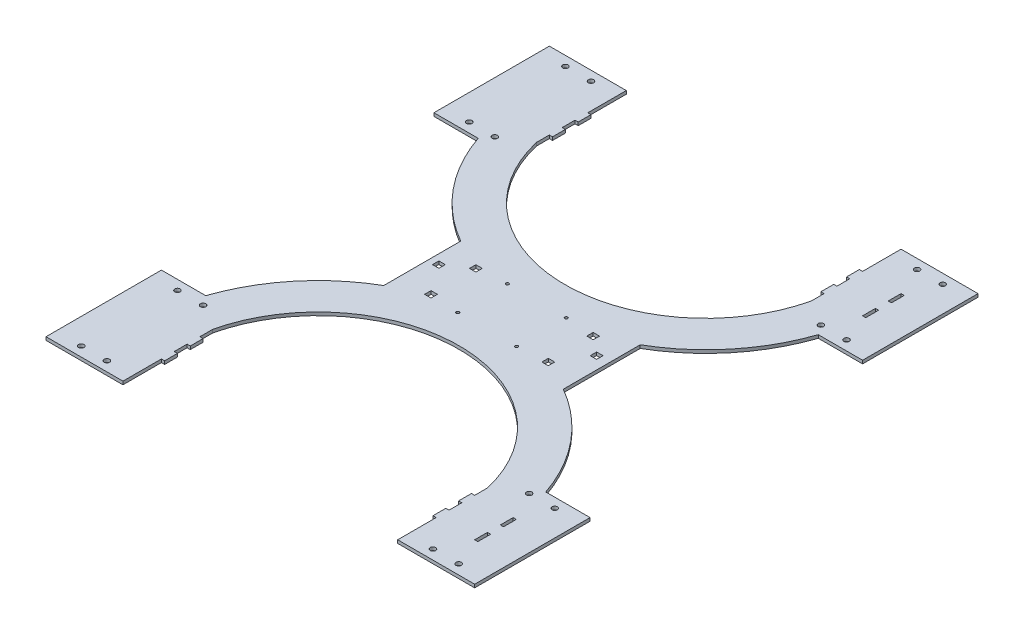
SolidWorks part; units mm, degrees
ref_plane "Front Plane" through (0, 0, 0) normal (0, 0, 1) x (1, 0, 0)
ref_plane "Top Plane" through (0, 0, 0) normal (0, 1, 0) x (1, 0, 0)
ref_plane "Right Plane" through (0, 0, 0) normal (1, 0, 0) x (0, 0, -1)
sketch "Sketch1" plane through (0, 0, 0) normal (0, 1, 0) x (1, 0, 0)
  line L47 (-136.0442, 57.15) -> (-212.2442, 57.15)
  line L49 (-212.2442, -57.15) -> (-168.3648, -57.15)
  line L51 (-88.9, -153.9793) -> (-88.9, -230.1793)
  line L60 (136.0442, 57.15) -> (212.2442, 57.15)
  line L62 (212.2442, -57.15) -> (168.3648, -57.15)
  line L64 (88.9, -153.9793) -> (88.9, -230.1793)
  line L65 (-136.0442, -31.75) -> (-136.0442, -19.05)
  line L66 (0, 0) -> (136.0442, 0) construction
  line L67 (0, -167.5048) -> (0, 0) construction
  line L68 (-88.9, -192.0793) -> (88.9, -192.0793) construction
  line L72 (136.0442, -365.1086) -> (136.0442, -352.4086)
  line L98 (212.2442, 57.15) -> (212.2442, -57.15)
  line L103 (-212.2442, 57.15) -> (-212.2442, -57.15)
  line L133 (136.0442, 19.05) -> (136.0442, 57.15)
  line L142 (-136.0442, -352.4086) -> (-136.0442, -365.1086)
  line L151 (136.0442, -403.2086) -> (136.0442, -441.3086)
  line L152 (-212.2442, -441.3086) -> (-212.2442, -327.0086)
  line L153 (212.2442, -441.3086) -> (212.2442, -327.0086)
  line L154 (212.2442, -327.0086) -> (168.3648, -327.0086)
  line L155 (136.0442, -441.3086) -> (212.2442, -441.3086)
  line L159 (-212.2442, -327.0086) -> (-168.3648, -327.0086)
  line L160 (-136.0442, -441.3086) -> (-212.2442, -441.3086)
  line L166 (-161.4442, 47.625) -> (-186.8442, 47.625) construction
  line L167 (161.4442, 47.625) -> (186.8442, 47.625) construction
  line L168 (186.8442, 47.625) -> (186.8442, -47.625) construction
  line L169 (186.8442, -47.625) -> (161.4442, -47.625) construction
  line L170 (-186.8442, 47.625) -> (-186.8442, -47.625) construction
  line L171 (-186.8442, -47.625) -> (-161.4442, -47.625) construction
  line L172 (-29.1465, -167.5048) -> (29.1465, -167.5048) construction
  line L173 (29.1465, -167.5048) -> (29.1465, -216.6538) construction
  line L174 (29.1465, -216.6538) -> (-29.1465, -216.6538) construction
  line L175 (174.1442, -6.35) -> (174.1442, 6.35) construction
  line L176 (-136.0442, -19.05) -> (-132.8692, -19.05)
  line L177 (-132.8692, -19.05) -> (-132.8692, -6.35)
  line L178 (-132.8692, -6.35) -> (-136.0442, -6.35)
  line L179 (-136.0442, -6.35) -> (-136.0442, 6.35)
  line L180 (-136.0442, 6.35) -> (-132.8692, 6.35)
  line L181 (-132.8692, 6.35) -> (-132.8692, 19.05)
  line L182 (-132.8692, 19.05) -> (-136.0442, 19.05)
  line L183 (-136.0442, 19.05) -> (-136.0442, 57.15)
  line L184 (-136.0442, 0) -> (0, 0) construction
  line L185 (-136.0442, -365.1086) -> (-132.8692, -365.1086)
  line L186 (-132.8692, -365.1086) -> (-132.8692, -377.8086)
  line L187 (-132.8692, -377.8086) -> (-136.0442, -377.8086)
  line L188 (-136.0442, -377.8086) -> (-136.0442, -390.5086)
  line L189 (-136.0442, -390.5086) -> (-132.8692, -390.5086)
  line L190 (-132.8692, -390.5086) -> (-132.8692, -403.2086)
  line L191 (-132.8692, -403.2086) -> (-136.0442, -403.2086)
  line L192 (-136.0442, -403.2086) -> (-136.0442, -441.3086)
  line L193 (136.0442, 19.05) -> (132.8692, 19.05)
  line L194 (132.8692, 19.05) -> (132.8692, 6.35)
  line L195 (132.8692, 6.35) -> (136.0442, 6.35)
  line L196 (136.0442, 6.35) -> (136.0442, -6.35)
  line L197 (136.0442, -6.35) -> (132.8692, -6.35)
  line L198 (132.8692, -6.35) -> (132.8692, -19.05)
  line L199 (132.8692, -19.05) -> (136.0442, -19.05)
  line L200 (136.0442, -19.05) -> (136.0442, -31.75)
  line L201 (132.8692, -365.1086) -> (136.0442, -365.1086)
  line L202 (132.8692, -377.8086) -> (132.8692, -365.1086)
  line L203 (136.0442, -377.8086) -> (132.8692, -377.8086)
  line L204 (136.0442, -390.5086) -> (136.0442, -377.8086)
  line L205 (132.8692, -390.5086) -> (136.0442, -390.5086)
  line L206 (132.8692, -403.2086) -> (132.8692, -390.5086)
  line L207 (136.0442, -403.2086) -> (132.8692, -403.2086)
  line L208 (174.1442, 19.05) -> (177.3192, 19.05)
  line L209 (174.1442, 19.05) -> (174.1442, 6.35)
  line L210 (174.1442, 6.35) -> (177.3192, 6.35)
  line L211 (177.3192, 19.05) -> (177.3192, 6.35)
  line L212 (174.1442, -6.35) -> (177.3192, -6.35)
  line L213 (174.1442, -6.35) -> (174.1442, -19.05)
  line L214 (174.1442, -19.05) -> (177.3192, -19.05)
  line L215 (177.3192, -6.35) -> (177.3192, -19.05)
  line L216 (136.0442, 0) -> (174.1442, 0) construction
  line L217 (174.1442, -377.8086) -> (174.1442, -365.1086)
  line L218 (174.1442, -365.1086) -> (177.3192, -365.1086)
  line L219 (177.3192, -377.8086) -> (177.3192, -365.1086)
  line L220 (174.1442, -377.8086) -> (177.3192, -377.8086)
  line L221 (174.1442, -390.5086) -> (177.3192, -390.5086)
  line L222 (174.1442, -403.2086) -> (174.1442, -390.5086)
  line L223 (177.3192, -403.2086) -> (177.3192, -390.5086)
  line L224 (174.1442, -403.2086) -> (177.3192, -403.2086)
  line L225 (-54.7929, -173.0293) -> (-54.7929, -192.0793) construction
  line L226 (-61.1429, -166.6793) -> (-54.7929, -166.6793)
  line L227 (-61.1429, -166.6793) -> (-61.1429, -173.0293)
  line L228 (-61.1429, -173.0293) -> (-54.7929, -173.0293)
  line L229 (-54.7929, -166.6793) -> (-54.7929, -173.0293)
  line L230 (54.9714, -166.6793) -> (61.3214, -166.6793)
  line L231 (54.9714, -166.6793) -> (54.9714, -173.0293)
  line L232 (54.9714, -173.0293) -> (61.3214, -173.0293)
  line L233 (61.3214, -166.6793) -> (61.3214, -173.0293)
  line L234 (54.9714, -211.1293) -> (61.3214, -211.1293)
  line L235 (54.9714, -211.1293) -> (54.9714, -217.4793)
  line L236 (54.9714, -217.4793) -> (61.3214, -217.4793)
  line L237 (61.3214, -211.1293) -> (61.3214, -217.4793)
  line L238 (-61.1429, -211.1293) -> (-54.7929, -211.1293)
  line L239 (-61.1429, -211.1293) -> (-61.1429, -217.4793)
  line L240 (-61.1429, -217.4793) -> (-54.7929, -217.4793)
  line L241 (-54.7929, -211.1293) -> (-54.7929, -217.4793)
  line L242 (73.4754, -181.7472) -> (79.8254, -181.7472)
  line L243 (73.4754, -181.7472) -> (73.4754, -188.0972)
  line L244 (73.4754, -188.0972) -> (79.8254, -188.0972)
  line L245 (79.8254, -181.7472) -> (79.8254, -188.0972)
  line L246 (-82.7346, -181.7472) -> (-76.3846, -181.7472)
  line L247 (-82.7346, -181.7472) -> (-82.7346, -188.0972)
  line L248 (-82.7346, -188.0972) -> (-76.3846, -188.0972)
  line L249 (-76.3846, -181.7472) -> (-76.3846, -188.0972)
  arc A14 (88.9, -153.9793) -> (168.3648, -57.15) centre (0, 0) ccw
  arc A15 (-88.9, -153.9793) -> (-168.3648, -57.15) centre (0, 0) cw
  arc A23 (88.9, -230.1793) -> (168.3648, -327.0086) centre (0, -384.1586) cw
  arc A26 (-88.9, -230.1793) -> (-168.3648, -327.0086) centre (0, -384.1586) ccw
  circle A27 centre (186.8442, 47.625) radius 2.667
  circle A28 centre (161.4442, 47.625) radius 2.667
  circle A29 centre (186.8442, -47.625) radius 2.667
  circle A30 centre (161.4442, -47.625) radius 2.667
  circle A31 centre (161.4442, -336.5336) radius 2.667
  circle A32 centre (186.8442, -336.5336) radius 2.667
  circle A33 centre (186.8442, -431.7836) radius 2.667
  circle A34 centre (161.4442, -431.7836) radius 2.667
  circle A35 centre (-186.8442, 47.625) radius 2.667
  circle A36 centre (-161.4442, 47.625) radius 2.667
  circle A37 centre (-186.8442, -47.625) radius 2.667
  circle A38 centre (-161.4442, -47.625) radius 2.667
  circle A39 centre (-186.8442, -336.5336) radius 2.667
  circle A40 centre (-161.4442, -336.5336) radius 2.667
  circle A41 centre (-161.4442, -431.7836) radius 2.667
  circle A42 centre (-186.8442, -431.7836) radius 2.667
  circle A43 centre (-29.1465, -167.5048) radius 1.4605
  circle A44 centre (29.1465, -167.5048) radius 1.4605
  circle A45 centre (29.1465, -216.6538) radius 1.4605
  circle A46 centre (-29.1465, -216.6538) radius 1.4605
  arc A47 (-136.0442, -31.75) -> (136.0442, -31.75) centre (0, 0) ccw
  arc A48 (-136.0442, -352.4086) -> (136.0442, -352.4086) centre (0, -384.1586) cw
  point P96 (29.1465, -192.0793)
  point P108 (136.0442, 0)
  dimension "D5" = 3.175
  dimension "D7" = 5.334
  dimension "D8" = 12.7
  dimension "D9" = 12.7
  dimension "D10" = 12.7
  dimension "D11" = 12.7
  dimension "D12" = 76.2
  dimension "D13" = 50.8
  dimension "D4" = 12.7
  dimension "D2" = 177.8
  dimension "D6" = 139.7
  dimension "D14" = 9.525
  dimension "D17" = 5.334
  dimension "D27" = 2.921
  dimension "D3" = 12.7
  dimension "D15" = 177.8
  dimension "D16" = 9.525
  dimension "D18" = 38.1
  dimension "D19" = 25.4
  dimension "D20" = 3.175
  dimension "D21" = 76.2
  dimension "D22" = 9.525
  dimension "D23" = 9.525
  dimension "D24" = 50.8
  dimension "D25" = 25.4
  dimension "D26" = 114.3
  dimension "D28" = 58.293
  dimension "D29" = 49.149
  dimension "D30" = 12.7
  dimension "D31" = 3.175
  dimension "D32" = 38.1
  dimension "D33" = 12.7
  dimension "D34" = 6.35
  dimension "D35" = 38.1
  dimension "D36" = 149.86
  dimension "D37" = 19.05
  dimension "D38" = 38.1
extrude "Boss-Extrude1" add sketch "Sketch1" along normal blind 3.175
